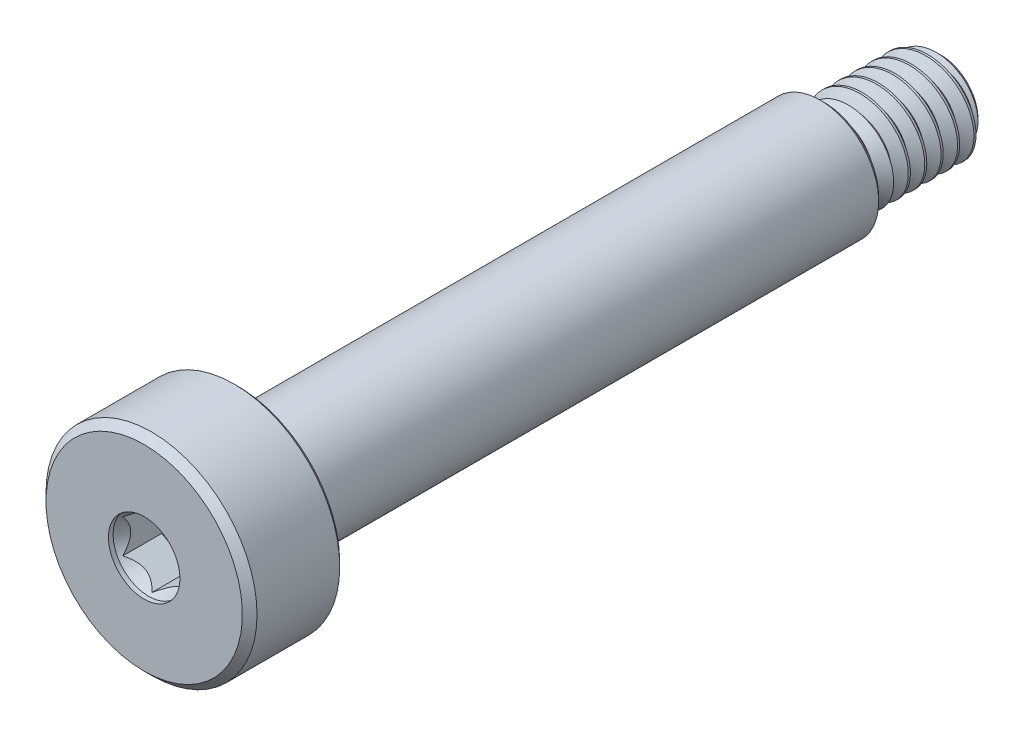
SolidWorks part; units mm, degrees
ref_plane "Front Plane" through (0, 0, 0) normal (0, 0, 1) x (1, 0, 0)
ref_plane "Top Plane" through (0, 0, 0) normal (0, 1, 0) x (1, 0, 0)
ref_plane "Right Plane" through (0, 0, 0) normal (1, 0, 0) x (0, 0, -1)
sketch "Sketch1" plane through (0, 0, 0) normal (1, 0, 0) x (0, 0, -1)
  line L0 (-17, 0) -> (17, 0) construction
  line L1 (-17, -4.5) -> (-17, 4.5)
  line L2 (-13, -4.5) -> (-13, 4.5)
  line L3 (12, 2.5) -> (12, -2.5)
  line L4 (-17, 1.25) -> (-17, -1.25)
  line L5 (17, 2) -> (17, -2)
  line L6 (16.9563, 2.0758) -> (17.6562, 2.0758) construction
  line L7 (17.6562, 2.0758) -> (17.3062, 1.4696) construction
  line L8 (17.3062, 1.4696) -> (16.9563, 2.0758) construction
  line L9 (17.3062, 2.0758) -> (17.3062, 2) construction
  line L10 (17.3062, 1.4696) -> (17.3062, 1.5453) construction
  line L11 (17, 2) -> (17.6125, 2) construction
  line L12 (16.9781, 2.0379) -> (17.6344, 2.0379) construction
  line L13 (17.2625, 1.5453) -> (17.35, 1.5453) construction
  line L14 (-13, 0) -> (-10.5, 0) construction
  line L15 (-10.5, 0) -> (9.5, 0) construction
  line L16 (9.5, 0) -> (12, 0) construction
  point P0 (14.55, -2)
  point P4 (0, 0)
  point P8 (-17, 0)
  point P11 (-13, 0)
  point P14 (12, 0)
  point P17 (-17, 0)
  point P20 (17, 0)
  point P28 (17.3062, 2)
  point P32 (17.3062, 2.0379)
  point P35 (17.3062, 1.5453)
  point P36 (17, 2.5)
  dimension "D1" = 2.45
  dimension "D3" = 0.0875
  dimension "D2" = 20
sketch "Sketch2" plane through (0, 0, 0) normal (1, 0, 0) x (0, 0, -1)
  line L0 (17, 0) -> (17, 1.5625)
  line L2 (17, 1.5625) -> (16.5625, 2)
  line L3 (16.5625, 2) -> (13.032, 2)
  line L4 (13.032, 2) -> (12.5773, 1.5453)
  line L5 (12.5773, 1.5453) -> (12.2273, 1.5453)
  line L6 (17.3062, 1.4696) -> (16.9563, 2.0758) construction
  line L7 (12, 1.7727) -> (12, 2.325)
  line L8 (11.825, 2.5) -> (-11.9368, 2.5)
  line L9 (-11.9368, 2.5) -> (-12.2888, 2.2968)
  line L10 (-12.2888, 2.2968) -> (-12.3777, 2.2968)
  line L11 (-13, -4.5) -> (-13, 4.5) construction
  line L12 (-17, -4.5) -> (-17, 4.5) construction
  line L13 (-13.16, 4.5) -> (-16.6876, 4.5)
  line L14 (-17, 4.1876) -> (-17, 0)
  line L15 (-17, 0) -> (17, 0)
  line L16 (-16.6876, 4.5) -> (-17, 4.1876)
  line L17 (-13, 4.34) -> (-13, 2.9191)
  line L18 (11.825, 2.5) -> (12, 2.325)
  line L19 (12, 2.5) -> (12, -2.5) construction
  line L20 (-13.16, 4.5) -> (-13, 4.34)
  arc A0 (12.2273, 1.5453) -> (12, 1.7727) centre (12.2273, 1.7727) cw
  arc A1 (-12.3777, 2.2968) -> (-13, 2.9191) centre (-12.3777, 2.9191) cw
  point P23 (17.1313, 1.7727)
  dimension "D4" = 0.35
  dimension "D6" = 30
  dimension "D7" = 0.2032
  dimension "D8" = 0.3124
  dimension "D11" = 0.175
  dimension "D3" = 45
  dimension "D9" = 0.16
  dimension "D10" = 0.0889
  dimension "D5" = 0.7112
  dimension "D2" = 0.4375
revolve "Revolve1" add sketch "Sketch2" angle 360 about L15
sketch "Sketch3" plane through (0, 0, 17) normal (0, 0, 1) x (1, 0, 0)
  line L1 (0, 1.4434) -> (-1.25, 0.7217)
  line L2 (-1.25, 0.7217) -> (-1.25, -0.7217)
  line L3 (-1.25, -0.7217) -> (0, -1.4434)
  line L4 (0, -1.4434) -> (1.25, -0.7217)
  line L5 (1.25, -0.7217) -> (1.25, 0.7217)
  line L6 (1.25, 0.7217) -> (0, 1.4434)
  circle A0 centre (0, 0) radius 1.25 construction
  circle A1 centre (0, 0) radius 4.5 construction
  circle A2 centre (0, 0) radius 4.5 construction
extrude "Cut-Extrude1" cut sketch "Sketch3" against normal blind 2
sketch "Sketch4" plane through (0, 0, 17) normal (0, 0, 1) x (1, 0, 0)
  circle A0 centre (0, 0) radius 1.525
  dimension "D1" = 3.05
extrude "Cut-Extrude2" cut sketch "Sketch4" against normal blind 0.2
extrude "Cut-Extrude3" cut sketch "Sketch4<2>" against normal blind 1.5 draft 30 from surface starting at face at (1.525, 0, 16.8)
sketch "Sketch4<2>" plane through (0, 0, 17) normal (0, 0, 1) x (1, 0, 0) same geometry as "Sketch4"
ref_axis "Center Axis 1" through (0, 0, 15.9563) along (0, 0, -1)
ref_plane "Contact Plane 1" through (0, 0, 13) normal (0, 0, -1) x (-1, 0, 0)
sketch "Sketch5" plane through (0, 0, -17) normal (0, 0, -1) x (-1, 0, 0)
  circle A0 centre (0, 0) radius 2
curve "Helix/Spiral1" pitch 0.7 height 4.65 radius 2 centre (0, 0, -17) axis (0, 0, 1) start towards (0, 1, 0)
sketch "Sketch6" plane through (0, 0, 0) normal (1, 0, 0) x (0, 0, -1)
  line L0 (16.9781, 2.0379) -> (17.6344, 2.0379)
  line L1 (17.6344, 2.0379) -> (17.35, 1.5453)
  line L2 (17.35, 1.5453) -> (17.2625, 1.5453)
  line L3 (17.2625, 1.5453) -> (16.9781, 2.0379)
sweep "Cut-Sweep1" cut profiles "Sketch6" path "Helix/Spiral1"
equation "\"D3@Sketch1\" = \"Thread Pitch@Sketch1\" / 8"
equation "\"D1@Sketch1\" = \"Thread Pitch@Sketch1\" * 3.5"
equation "\"D4@Sketch2\" = \"Thread Pitch@Sketch1\" / 2"
equation "\"D8@Sketch2\"=\"Thread Size@Sketch1\" * .0781"
equation "\"D11@Sketch2\"=\"Thread Pitch@Sketch1\" * .25"
equation "\"D1@Cut-Extrude1\" = \"Thread Size@Sketch1\" * .5"
equation "\"D1@Cut-Extrude2\"=\"D1@Cut-Extrude1\" * .1"
equation "\"D4@Helix/Spiral1\" = \"Thread Pitch@Sketch1\""
equation "\"D3@Helix/Spiral1\" = \"Thread Length@Sketch1\" - ( \"Thread Pitch@Sketch1\" / 2 )"
equation "\"D2@Sketch1\"=\"Shoulder Length@Sketch1\"*.80"
equation "\"D1@Sketch4\"=\"Drive Size@Sketch1\" * 1.22"
equation "\"D9@Sketch2\"=\"thread size@sketch1\"*.04"
equation "\"D10@Sketch2\"=\"D5@Sketch2\"*.125"
equation "\"D1@Cut-Extrude3\" = \"D1@Cut-Extrude1\" * .75"
equation "\"D2@Sketch2\"=\"Thread Pitch@Sketch1\"*.625"
